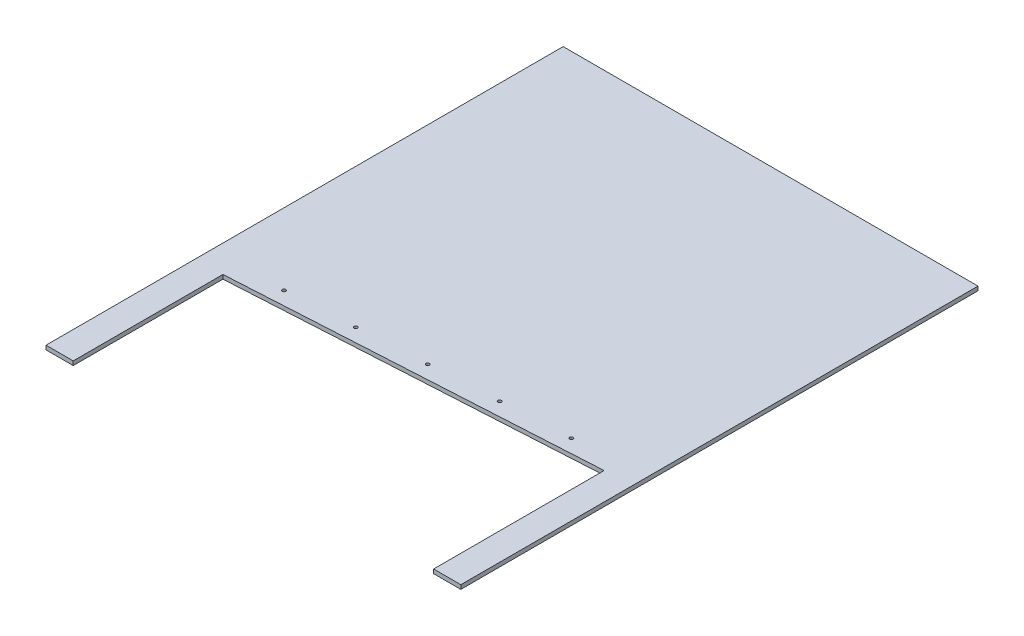
SolidWorks part; units mm, degrees
ref_plane "Front Plane" through (0, 0, 0) normal (0, 0, 1) x (1, 0, 0)
ref_plane "Top Plane" through (0, 0, 0) normal (0, 1, 0) x (1, 0, 0)
ref_plane "Right Plane" through (0, 0, 0) normal (1, 0, 0) x (0, 0, -1)
sketch "Sketch1" plane through (0, 0, 0) normal (0, 1, 0) x (1, 0, 0)
  line L0 (-152.4, -135) -> (-152.4, -245)
  line L1 (-152.4, 135) -> (152.4, 135)
  line L2 (-152.4, 135) -> (-152.4, -135)
  line L3 (-152.4, -135) -> (152.4, -135) construction
  line L4 (152.4, 135) -> (152.4, -135)
  line L5 (-152.4, 135) -> (152.4, -135) construction
  line L6 (-152.4, -135) -> (152.4, 135) construction
  line L7 (-152.4, -245) -> (-132.4, -245)
  line L8 (-132.4, -245) -> (-132.4, -135)
  line L9 (-132.4, -135) -> (132.4, -119.7231)
  line L10 (132.4, -119.7231) -> (132.4, -245)
  line L11 (132.4, -245) -> (152.4, -245)
  line L12 (152.4, -245) -> (152.4, -135)
  point P0 (0, 0)
  dimension "D1" = 304.8
  dimension "D2" = 270
  dimension "D3" = 110
  dimension "D4" = 110
  dimension "D5" = 20
  dimension "D6" = 20
  dimension "D7" = 3.302
extrude "Boss-Extrude1" add sketch "Sketch1" along normal blind 3
hole_wizard "M3 Tapped Hole1" positions "Sketch3" profile "Sketch2" tap size "M3" standard "ISO"
sketch "Sketch3" plane through (0, 3, 0) normal (0, 1, 0) x (1, 0, 0)
  line L0 (-132.4, -124.5827) -> (132.4, -109.3058) construction
  line L2 (-132.4, -135) -> (132.4, -119.7231) construction
  line L5 (0, -116.9442) -> (0.599, -127.327) construction
  point P0 (0, -116.9442)
  point P2 (-49.917, -119.8241)
  point P4 (-99.834, -122.7039)
  point P6 (49.917, -114.0644)
  point P8 (99.834, -111.1846)
  dimension "D1" = 10.4
  dimension "D2" = 50
  dimension "D3" = 100
  dimension "D4" = 50
  dimension "D5" = 100
sketch "Sketch2" plane through (0, 3, 116.9442) normal (1, 0, 0) x (0, 0, 1)
  line L0 (0, 0) -> (0, 8.2511)
  line L1 (0, 8.2511) -> (1.25, 7.5)
  line L2 (1.25, 7.5) -> (1.25, 0)
  line L5 (1.25, 0) -> (0, 0)
  line L10 (0, 8.2511) -> (-1.25, 7.5) construction
  line L11 (0, -6.35) -> (0, 107.95) construction
  dimension "Tap Drill Dia." = 2.5
  dimension "Tap Drill Depth" = 7.5
  dimension "Drill Angle" = 118
cosmetic thread "Hole Thread1" parameters "D1"=3, "D2"=3
cosmetic thread "Hole Thread2" parameters "D1"=3, "D2"=3
cosmetic thread "Hole Thread3" parameters "D1"=3, "D2"=3
cosmetic thread "Hole Thread4" parameters "D1"=3, "D2"=3
cosmetic thread "Hole Thread5" parameters "D1"=3, "D2"=3
equation "\"D7@Sketch1\"=atn( 15/260)"
